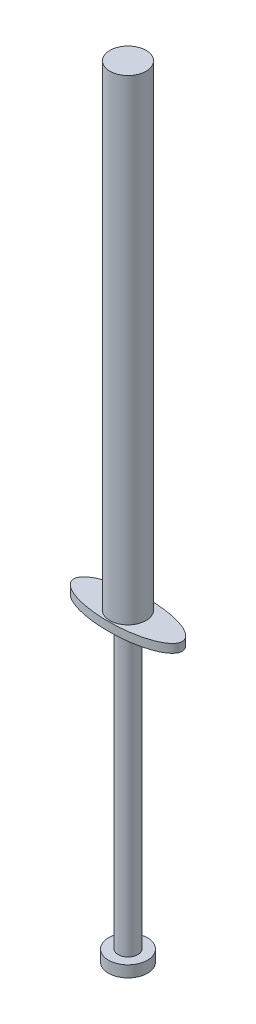
SolidWorks part; units mm, degrees
ref_plane "Front Plane" through (0, 0, 0) normal (0, 0, 1) x (1, 0, 0)
ref_plane "Top Plane" through (0, 0, 0) normal (0, 1, 0) x (1, 0, 0)
ref_plane "Right Plane" through (0, 0, 0) normal (1, 0, 0) x (0, 0, -1)
sketch "Sketch1" plane through (0, 0, 0) normal (0, 1, 0) x (1, 0, 0)
  circle A0 centre (0, 0) radius 3.175
extrude "Boss-Extrude1" add sketch "Sketch1" along normal blind 85
sketch "Sketch2" plane through (0, 0, 0) normal (0, 1, 0) x (1, 0, 0)
  ellipse E0 centre (0, 0) end of major axis (9.525, 0) minor radius 3.4557
extrude "Boss-Extrude2" add sketch "Sketch2" along normal blind 1.5
sketch "Sketch3" plane through (0, 0, 0) normal (0, 1, 0) x (1, 0, 0)
  circle A0 centre (0, 0) radius 1.7332
extrude "Boss-Extrude3" add sketch "Sketch3" against normal blind 50
sketch "Sketch4" plane through (0, -50, 0) normal (0, -1, 0) x (1, 0, 0)
  circle A0 centre (0, 0) radius 3.4158
extrude "Boss-Extrude4" add sketch "Sketch4" along normal blind 2
